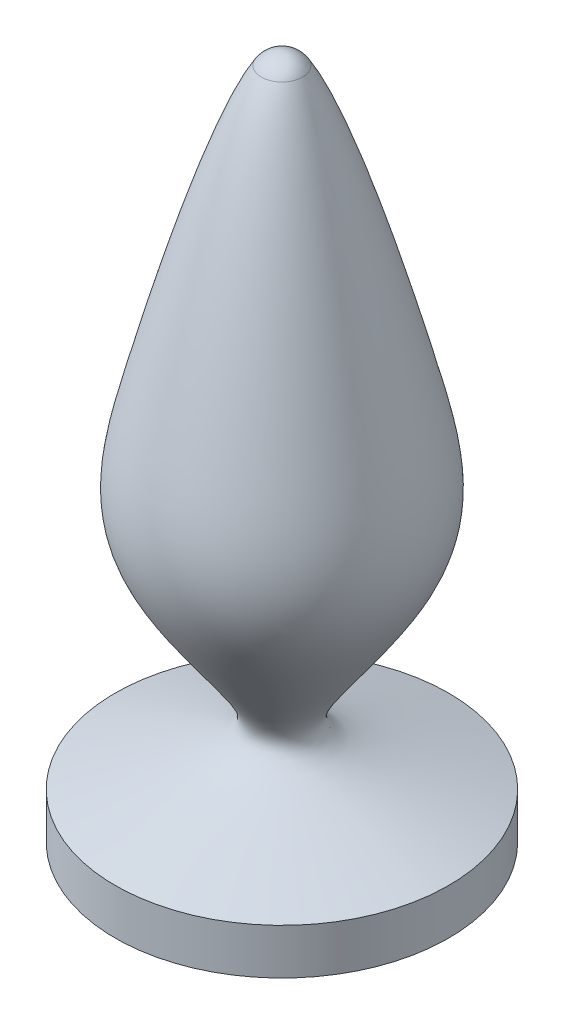
SolidWorks part; units mm, degrees
material "AISI 316 Stainless Steel Sheet (SS)"
ref_plane "Front Plane" through (0, 0, 0) normal (0, 0, 1) x (1, 0, 0)
ref_plane "Top Plane" through (0, 0, 0) normal (0, 1, 0) x (1, 0, 0)
ref_plane "Right Plane" through (0, 0, 0) normal (1, 0, 0) x (0, 0, -1)
sketch "Sketch1" plane through (0, 0, 0) normal (0, 0, 1) x (1, 0, 0)
  line L0 (0, -71.3772) -> (0, 0)
  line L2 (17.399, -66.6147) -> (17.399, -71.3772)
  line L3 (17.399, -71.3772) -> (0, -71.3772)
  arc A0 (2.1447, -1.1792) -> (0, 0) centre (0, -2.54) ccw
  spline S0 degree 3 poles (2.1447, -1.1792) (4.7028, -5.2108) (8.98, -18.8821) (14.5263, -40.9815) (12.2717, -46.216) (1.1462, -61.9245) (0.7386, -60.9479) (17.399, -66.6147) knots 0.105965 0.105965 0.105965 0.105965 0.448013 0.508175 0.685431 0.718366 1 1 1 1
  dimension "D2" = 3.302
  dimension "D3" = 4.7625
  dimension "D1" = 5.08
  dimension "D4" = 17.399
  dimension "D5" = 12.7
revolve "Revolve1" add sketch "Sketch1" angle 360 about L0
fillet "Fillet5" [suppressed] radius 0.508
sketch "Sketch9" [suppressed] plane through (0, 0, 0) normal (0, 0, 1) x (1, 0, 0)
  line L0 (0, 0) -> (0, -71.3772)
  line L1 (-17.399, -71.3772) -> (17.399, -71.3772) construction
  line L2 (17.399, -66.9786) -> (17.399, 0)
  line L3 (-17.399, -66.9786) -> (17.399, -66.9786) construction
  line L4 (0, 0) -> (17.399, 0)
  line L5 (13.3859, -65.2593) -> (13.3859, -39.3625)
  line L6 (13.3859, -39.3625) -> (13.3859, 0)
  arc A0 (17.399, -66.9786) -> (17.0543, -66.4975) centre (16.891, -66.9786) ccw construction
  arc A1 (2.1447, -1.1792) -> (-2.1447, -1.1792) centre (0, -2.54) ccw construction
  arc A2 (2.1447, -1.1792) -> (0, 0) centre (0, -2.54) ccw
  spline S0 degree 3 poles (1016.4528, 2761.8004) (40.2905, -74.737) (28.6858, -70.4456) (16.4956, -66.3079) (15.6352, -66.0169) (14.4859, -65.6297) (13.5033, -65.299) (12.6028, -64.9954) (11.7786, -64.7163) (11.0431, -64.4654) (10.3733, -64.2347) (9.7661, -64.0231) (9.203, -63.8239) (8.6784, -63.6349) (8.1808, -63.4517) (7.7188, -63.2774) (7.2801, -63.1069) (6.8944, -62.952) (6.5489, -62.8083) (6.2392, -62.6748) (5.9442, -62.5423) (5.6647, -62.4111) (5.4083, -62.2845) (5.1843, -62.1679) (4.9891, -62.0608) (4.8083, -61.9565) (4.6317, -61.8483) (4.4618, -61.737) (4.3066, -61.6275) (4.1673, -61.5214) (4.0427, -61.4185) (3.9294, -61.3167) (3.8224, -61.2112) (3.7197, -61.0988) (3.6251, -60.9813) (3.5404, -60.8598) (3.4733, -60.7469) (3.4159, -60.6326) (3.3725, -60.5288) (3.3376, -60.4253) (3.3094, -60.3212) (3.2864, -60.2042) (3.2716, -60.0749) (3.2666, -59.9443) (3.2708, -59.8136) (3.2836, -59.6821) (3.3049, -59.5476) (3.3345, -59.4106) (3.3741, -59.2634) (3.4252, -59.1045) (3.4885, -58.935) (3.5621, -58.7603) (3.6459, -58.5793) (3.7412, -58.3899) (3.8472, -58.1932) (3.9606, -57.9943) (4.0815, -57.792) (4.2194, -57.57) (4.3762, -57.3267) (4.5518, -57.0627) (4.7371, -56.7912) (4.9464, -56.4905) (5.1831, -56.1563) (5.4476, -55.7877) (5.7267, -55.4021) (6.0197, -54.999) (6.3486, -54.5468) (6.6412, -54.1435) (6.9823, -53.671) (7.3509, -53.1571) (7.7975, -52.5281) (8.2191, -51.9275) (8.5951, -51.3854) (8.9762, -50.8289) (9.3586, -50.2612) (9.7555, -49.658) (10.137, -49.0622) (10.5132, -48.4541) (10.8768, -47.8408) (11.2167, -47.2376) (11.533, -46.6422) (11.8258, -46.0517) (12.094, -45.4655) (12.3241, -44.9139) (12.5202, -44.3953) (12.6845, -43.9144) (12.8275, -43.4458) (12.9506, -42.9897) (13.0607, -42.522) (13.1576, -42.0349) (13.2385, -41.5342) (13.3019, -41.0275) (13.3508, -40.4841) (13.382, -39.8826) (13.3896, -39.2398) (13.3717, -38.5597) (13.327, -37.8504) (13.2557, -37.1294) (13.1851, -36.5861) (13.1162, -36.1173) (13.0482, -35.695) (12.952, -35.1551) (12.8428, -34.5906) (12.716, -33.9788) (12.568, -33.3066) (12.3911, -32.5441) (12.1909, -31.719) (11.9714, -30.8448) (11.7912, -30.1434) (11.3533, -28.4531) (10.822, -26.4429) (10.1329, -23.9126) (9.6167, -22.0565) (9.109, -20.2709) (8.6295, -18.621) (8.1649, -17.057) (7.71, -15.5604) (7.2702, -14.1481) (6.8552, -12.8481) (6.4697, -11.67) (6.1072, -10.5899) (5.7713, -9.6142) (5.4498, -8.7036) (5.138, -7.8443) (4.8389, -7.0434) (4.5553, -6.3063) (4.2946, -5.6491) (4.05, -5.0515) (3.8231, -4.514) (3.6023, -4.0079) (3.3953, -3.5497) (3.1997, -3.1321) (3.0195, -2.7609) (2.849, -2.4229) (2.6876, -2.1151) (2.5399, -1.8446) (2.401, -1.6006) (2.303, -1.4353) (2.2384, -1.3293) (2.2071, -1.2786) (-1.5226, 4.7074) (-12.3682, 6.1964) (2530.3734, 1612.9827) knots -0.467804 -0.467804 -0.467804 -0.467804 0.000052 0.001589 0.020751 0.034522 0.047614 0.060097 0.070588 0.080637 0.08959 0.097474 0.10504 0.112258 0.118636 0.125162 0.130998 0.136499 0.140935 0.1452 0.149297 0.153207 0.156918 0.160151 0.162788 0.165367 0.168073 0.170648 0.173075 0.17528 0.177293 0.179204 0.181062 0.182991 0.18498 0.186784 0.188608 0.189962 0.191634 0.192874 0.194107 0.195723 0.197395 0.199044 0.200678 0.202356 0.204055 0.205844 0.207673 0.209841 0.212176 0.214536 0.217035 0.219745 0.222583 0.225512 0.228436 0.231526 0.235429 0.239423 0.243556 0.247904 0.253326 0.259099 0.265121 0.271392 0.278013 0.286341 0.290299 0.300133 0.310338 0.319578 0.327981 0.335376 0.345177 0.353957 0.362776 0.372027 0.381093 0.389833 0.398304 0.406677 0.414844 0.422763 0.429357 0.435885 0.442046 0.447948 0.453811 0.46028 0.466792 0.473056 0.479657 0.487494 0.49591 0.504049 0.51331 0.522877 0.53154 0.534103 0.540858 0.547775 0.554913 0.562677 0.571487 0.581035 0.592384 0.603709 0.615242 0.619865 0.669975 0.694153 0.71939 0.743088 0.764604 0.784599 0.805004 0.82397 0.840734 0.856795 0.871012 0.88397 0.895957 0.907662 0.918661 0.928401 0.937636 0.945495 0.952904 0.959778 0.966451 0.971982 0.977279 0.982112 0.986346 0.990471 0.993807 0.997002 0.997764 0.998518 0.999263 1.265425 1.265425 1.265425 1.265425 only from (17.0543, -66.4975) to (2.1447, -1.1792) construction
  spline S1 degree 3 poles (17.0543, -66.4975) (16.5761, -66.3352) (15.7521, -66.0564) (14.599, -65.6678) (13.8731, -65.4235) (13.4932, -65.2955) (13.442, -65.2783) knots 0 0 0 0 0.019165 0.033015 0.04618 0.04823 0.04823 0.04823 0.04823
  spline S3 degree 3 poles (13.3859, -39.3625) (13.3859, -39.1047) (13.3744, -38.6029) (13.327, -37.8504) (13.2557, -37.1294) (13.1851, -36.5861) (13.1162, -36.1173) (13.0482, -35.695) (12.952, -35.1551) (12.8428, -34.5906) (12.716, -33.9788) (12.568, -33.3066) (12.3911, -32.5441) (12.1909, -31.719) (11.9714, -30.8448) (11.7912, -30.1434) (11.3533, -28.4531) (10.822, -26.4429) (10.1329, -23.9126) (9.6167, -22.0565) (9.109, -20.2709) (8.6295, -18.621) (8.1649, -17.057) (7.71, -15.5604) (7.2702, -14.1481) (6.8552, -12.8481) (6.4697, -11.67) (6.1072, -10.5899) (5.7713, -9.6142) (5.4498, -8.7036) (5.138, -7.8443) (4.8389, -7.0434) (4.5553, -6.3063) (4.2946, -5.6491) (4.05, -5.0515) (3.8231, -4.514) (3.6023, -4.0079) (3.3953, -3.5497) (3.1997, -3.1321) (3.0195, -2.7609) (2.849, -2.4229) (2.6876, -2.1151) (2.5399, -1.8446) (2.401, -1.6006) (2.303, -1.4353) (2.2384, -1.3293) (2.2071, -1.2786) (2.1759, -1.2286) (2.1551, -1.1956) (2.1447, -1.1792) knots 0.494266 0.494266 0.494266 0.494266 0.504049 0.51331 0.522877 0.53154 0.534103 0.540858 0.547775 0.554913 0.562677 0.571487 0.581035 0.592384 0.603709 0.615242 0.619865 0.669975 0.694153 0.71939 0.743088 0.764604 0.784599 0.805004 0.82397 0.840734 0.856795 0.871012 0.88397 0.895957 0.907662 0.918661 0.928401 0.937636 0.945495 0.952904 0.959778 0.966451 0.971982 0.977279 0.982112 0.986346 0.990471 0.993807 0.997002 0.997764 0.998518 0.999263 1 1 1 1
  point P18 (13.3859, -39.3625)
  point P20 (13.3859, -65.2593)
sketch "Sketch8" plane through (0, 0, 0) normal (0, 0, 1) x (1, 0, 0)
  line L0 (0, 97.852) -> (0, -97.852)
  line L1 (0, -97.852) -> (-27.3156, -97.852)
  line L2 (-27.3156, -97.852) -> (-27.3156, 97.852)
  line L3 (-27.3156, 97.852) -> (0, 97.852)
  point P4 (0, 0)
extrude "Cut-Extrude4" [suppressed] cut sketch "Sketch8" against normal blind 25.4 and the other way blind 25.4
sketch "Sketch11" [suppressed] plane through (0, 0, 0) normal (0, 0, 1) x (1, 0, 0)
  line L5 (13.3859, -65.2593) -> (13.3859, -39.3625)
  spline S2 degree 3 poles (13.442, -65.2783) (13.0798, -65.1562) (12.4576, -64.9464) (11.5853, -64.6505) (10.8581, -64.402) (10.1979, -64.1739) (9.6023, -63.9654) (9.0448, -63.7673) (8.5198, -63.577) (8.0256, -63.3937) (7.5695, -63.22) (7.1428, -63.0524) (6.7634, -62.8982) (6.424, -62.7551) (6.119, -62.6215) (5.8306, -62.4897) (5.5602, -62.3603) (5.3115, -62.2349) (5.0934, -62.1188) (4.898, -62.009) (4.7186, -61.9023) (4.545, -61.7925) (4.3815, -61.6814) (4.2343, -61.5735) (4.1029, -61.4693) (3.9849, -61.3677) (3.8762, -61.2655) (3.771, -61.1566) (3.6722, -61.0418) (3.5815, -60.921) (3.509, -60.8088) (3.4516, -60.7052) (3.402, -60.6016) (3.3612, -60.498) (3.3285, -60.3942) (3.3024, -60.2895) (3.2817, -60.1718) (3.2694, -60.0422) (3.2668, -59.9116) (3.2732, -59.781) (3.2882, -59.6488) (3.3116, -59.5135) (3.3432, -59.3757) (3.3855, -59.2254) (3.4395, -59.064) (3.5059, -58.8919) (3.582, -58.7158) (3.6687, -58.5327) (3.7669, -58.3411) (3.8748, -58.1438) (3.9902, -57.9441) (4.1128, -57.7409) (4.2525, -57.5181) (4.4109, -57.2739) (4.5879, -57.0093) (4.7754, -56.7357) (4.987, -56.4327) (5.2263, -56.0957) (5.493, -55.7248) (5.7744, -55.3363) (6.0698, -54.9301) (6.3829, -54.4996) (6.6586, -54.1194) (6.9823, -53.671) (7.3509, -53.1571) (7.7975, -52.5281) (8.2191, -51.9275) (8.5951, -51.3854) (8.9762, -50.8289) (9.3586, -50.2612) (9.7555, -49.658) (10.137, -49.0622) (10.5132, -48.4541) (10.8768, -47.8408) (11.2167, -47.2376) (11.533, -46.6422) (11.8258, -46.0517) (12.094, -45.4655) (12.3241, -44.9139) (12.5202, -44.3953) (12.6845, -43.9144) (12.8275, -43.4458) (12.9506, -42.9897) (13.0607, -42.522) (13.1576, -42.0349) (13.2385, -41.5342) (13.3019, -41.0275) (13.3508, -40.4841) (13.3798, -39.9259) (13.3859, -39.5409) (13.3859, -39.3625) knots 0.04823 0.04823 0.04823 0.04823 0.062735 0.073149 0.08319 0.091898 0.099658 0.107139 0.114352 0.12085 0.127141 0.132875 0.138247 0.142684 0.146854 0.150885 0.154715 0.158231 0.161456 0.164092 0.166737 0.169376 0.171887 0.174234 0.176302 0.178254 0.180143 0.181963 0.183996 0.18589 0.18769 0.189062 0.190383 0.192048 0.193285 0.194511 0.19614 0.197816 0.199449 0.201094 0.202776 0.204496 0.206301 0.20814 0.210421 0.212756 0.215143 0.217701 0.220442 0.223314 0.226231 0.229197 0.232319 0.236213 0.240244 0.244398 0.2488 0.254269 0.260086 0.266136 0.272476 0.279145 0.286341 0.290299 0.300133 0.310338 0.319578 0.327981 0.335376 0.345177 0.353957 0.362776 0.372027 0.381093 0.389833 0.398304 0.406677 0.414844 0.422763 0.429357 0.435885 0.442046 0.447948 0.453811 0.46028 0.466792 0.473056 0.479657 0.487494 0.494266 0.494266 0.494266 0.494266
  point P18 (13.3859, -39.3625)
  point P20 (13.3859, -65.2593)
sketch "Sketch12" [suppressed] plane through (0, 0, 0) normal (0, 0, 1) x (1, 0, 0)
  line L0 (0, 0) -> (0, -71.3772)
  line L2 (17.399, -66.9786) -> (17.399, 0)
  line L4 (0, 0) -> (17.399, 0)
  line L5 (13.3859, -65.2593) -> (13.3859, -39.3625)
  line L6 (13.3859, -39.3625) -> (13.3859, 0)
  arc A2 (2.1447, -1.1792) -> (0, 0) centre (0, -2.54) ccw
  spline S1 degree 3 poles (17.0543, -66.4975) (16.5761, -66.3352) (15.7521, -66.0564) (14.599, -65.6678) (13.8731, -65.4235) (13.4932, -65.2955) (13.442, -65.2783) knots 0 0 0 0 0.019165 0.033015 0.04618 0.04823 0.04823 0.04823 0.04823
  spline S2 degree 3 poles (13.442, -65.2783) (13.0798, -65.1562) (12.4576, -64.9464) (11.5853, -64.6505) (10.8581, -64.402) (10.1979, -64.1739) (9.6023, -63.9654) (9.0448, -63.7673) (8.5198, -63.577) (8.0256, -63.3937) (7.5695, -63.22) (7.1428, -63.0524) (6.7634, -62.8982) (6.424, -62.7551) (6.119, -62.6215) (5.8306, -62.4897) (5.5602, -62.3603) (5.3115, -62.2349) (5.0934, -62.1188) (4.898, -62.009) (4.7186, -61.9023) (4.545, -61.7925) (4.3815, -61.6814) (4.2343, -61.5735) (4.1029, -61.4693) (3.9849, -61.3677) (3.8762, -61.2655) (3.771, -61.1566) (3.6722, -61.0418) (3.5815, -60.921) (3.509, -60.8088) (3.4516, -60.7052) (3.402, -60.6016) (3.3612, -60.498) (3.3285, -60.3942) (3.3024, -60.2895) (3.2817, -60.1718) (3.2694, -60.0422) (3.2668, -59.9116) (3.2732, -59.781) (3.2882, -59.6488) (3.3116, -59.5135) (3.3432, -59.3757) (3.3855, -59.2254) (3.4395, -59.064) (3.5059, -58.8919) (3.582, -58.7158) (3.6687, -58.5327) (3.7669, -58.3411) (3.8748, -58.1438) (3.9902, -57.9441) (4.1128, -57.7409) (4.2525, -57.5181) (4.4109, -57.2739) (4.5879, -57.0093) (4.7754, -56.7357) (4.987, -56.4327) (5.2263, -56.0957) (5.493, -55.7248) (5.7744, -55.3363) (6.0698, -54.9301) (6.3829, -54.4996) (6.6586, -54.1194) (6.9823, -53.671) (7.3509, -53.1571) (7.7975, -52.5281) (8.2191, -51.9275) (8.5951, -51.3854) (8.9762, -50.8289) (9.3586, -50.2612) (9.7555, -49.658) (10.137, -49.0622) (10.5132, -48.4541) (10.8768, -47.8408) (11.2167, -47.2376) (11.533, -46.6422) (11.8258, -46.0517) (12.094, -45.4655) (12.3241, -44.9139) (12.5202, -44.3953) (12.6845, -43.9144) (12.8275, -43.4458) (12.9506, -42.9897) (13.0607, -42.522) (13.1576, -42.0349) (13.2385, -41.5342) (13.3019, -41.0275) (13.3508, -40.4841) (13.3798, -39.9259) (13.3859, -39.5409) (13.3859, -39.3625) knots 0.04823 0.04823 0.04823 0.04823 0.062735 0.073149 0.08319 0.091898 0.099658 0.107139 0.114352 0.12085 0.127141 0.132875 0.138247 0.142684 0.146854 0.150885 0.154715 0.158231 0.161456 0.164092 0.166737 0.169376 0.171887 0.174234 0.176302 0.178254 0.180143 0.181963 0.183996 0.18589 0.18769 0.189062 0.190383 0.192048 0.193285 0.194511 0.19614 0.197816 0.199449 0.201094 0.202776 0.204496 0.206301 0.20814 0.210421 0.212756 0.215143 0.217701 0.220442 0.223314 0.226231 0.229197 0.232319 0.236213 0.240244 0.244398 0.2488 0.254269 0.260086 0.266136 0.272476 0.279145 0.286341 0.290299 0.300133 0.310338 0.319578 0.327981 0.335376 0.345177 0.353957 0.362776 0.372027 0.381093 0.389833 0.398304 0.406677 0.414844 0.422763 0.429357 0.435885 0.442046 0.447948 0.453811 0.46028 0.466792 0.473056 0.479657 0.487494 0.494266 0.494266 0.494266 0.494266
  spline S3 degree 3 poles (13.3859, -39.3625) (13.3859, -39.1047) (13.3744, -38.6029) (13.327, -37.8504) (13.2557, -37.1294) (13.1851, -36.5861) (13.1162, -36.1173) (13.0482, -35.695) (12.952, -35.1551) (12.8428, -34.5906) (12.716, -33.9788) (12.568, -33.3066) (12.3911, -32.5441) (12.1909, -31.719) (11.9714, -30.8448) (11.7912, -30.1434) (11.3533, -28.4531) (10.822, -26.4429) (10.1329, -23.9126) (9.6167, -22.0565) (9.109, -20.2709) (8.6295, -18.621) (8.1649, -17.057) (7.71, -15.5604) (7.2702, -14.1481) (6.8552, -12.8481) (6.4697, -11.67) (6.1072, -10.5899) (5.7713, -9.6142) (5.4498, -8.7036) (5.138, -7.8443) (4.8389, -7.0434) (4.5553, -6.3063) (4.2946, -5.6491) (4.05, -5.0515) (3.8231, -4.514) (3.6023, -4.0079) (3.3953, -3.5497) (3.1997, -3.1321) (3.0195, -2.7609) (2.849, -2.4229) (2.6876, -2.1151) (2.5399, -1.8446) (2.401, -1.6006) (2.303, -1.4353) (2.2384, -1.3293) (2.2071, -1.2786) (2.1759, -1.2286) (2.1551, -1.1956) (2.1447, -1.1792) knots 0.494266 0.494266 0.494266 0.494266 0.504049 0.51331 0.522877 0.53154 0.534103 0.540858 0.547775 0.554913 0.562677 0.571487 0.581035 0.592384 0.603709 0.615242 0.619865 0.669975 0.694153 0.71939 0.743088 0.764604 0.784599 0.805004 0.82397 0.840734 0.856795 0.871012 0.88397 0.895957 0.907662 0.918661 0.928401 0.937636 0.945495 0.952904 0.959778 0.966451 0.971982 0.977279 0.982112 0.986346 0.990471 0.993807 0.997002 0.997764 0.998518 0.999263 1 1 1 1
  point P18 (13.3859, -39.3625)
  point P20 (13.3859, -65.2593)
sketch "Sketch7" [suppressed] plane through (0, 0, 0) normal (0, 0, 1) x (1, 0, 0)
  line L0 (0, 36.2888) -> (0, -36.443)
  line L1 (0, -36.443) -> (16.7485, -36.443)
  spline S3 degree 3 poles (16.7485, -36.443) (16.6964, -36.421) (16.1852, -36.2034) (14.7412, -35.5632) (12.3997, -34.3922) (9.52, -32.6081) (7.0407, -30.5489) (5.1322, -28.2141) (3.8773, -26.0184) (3.0367, -23.4156) (2.8006, -20.7092) (3.0825, -18.2479) (3.8584, -15.442) (5.1532, -12.6994) (6.7245, -10.0601) (8.1892, -7.7756) (9.4485, -5.7298) (10.397, -3.9042) (10.9183, -2.4334) (11.2269, -0.7681) (11.2961, 1.0712) (11.0861, 3.7785) (10.3136, 7.5197) (8.8894, 12.4167) (7.3232, 17.3646) (5.6401, 22.2719) (3.8492, 27.1382) (2.2643, 31.1313) (1.0083, 34.0755) (0.3568, 35.5233) (0.0436, 36.1956) (0, 36.2888) knots 0.013851 0.013851 0.013851 0.013851 0.015625 0.03125 0.0625 0.09375 0.125 0.140625 0.15625 0.171875 0.1875 0.203125 0.21875 0.25 0.28125 0.3125 0.34375 0.375 0.40625 0.4375 0.46875 0.5 0.5625 0.625 0.6875 0.75 0.8125 0.875 0.90625 0.93044 0.934346 0.934346 0.934346 0.934346
  point P4 (0, 0)
